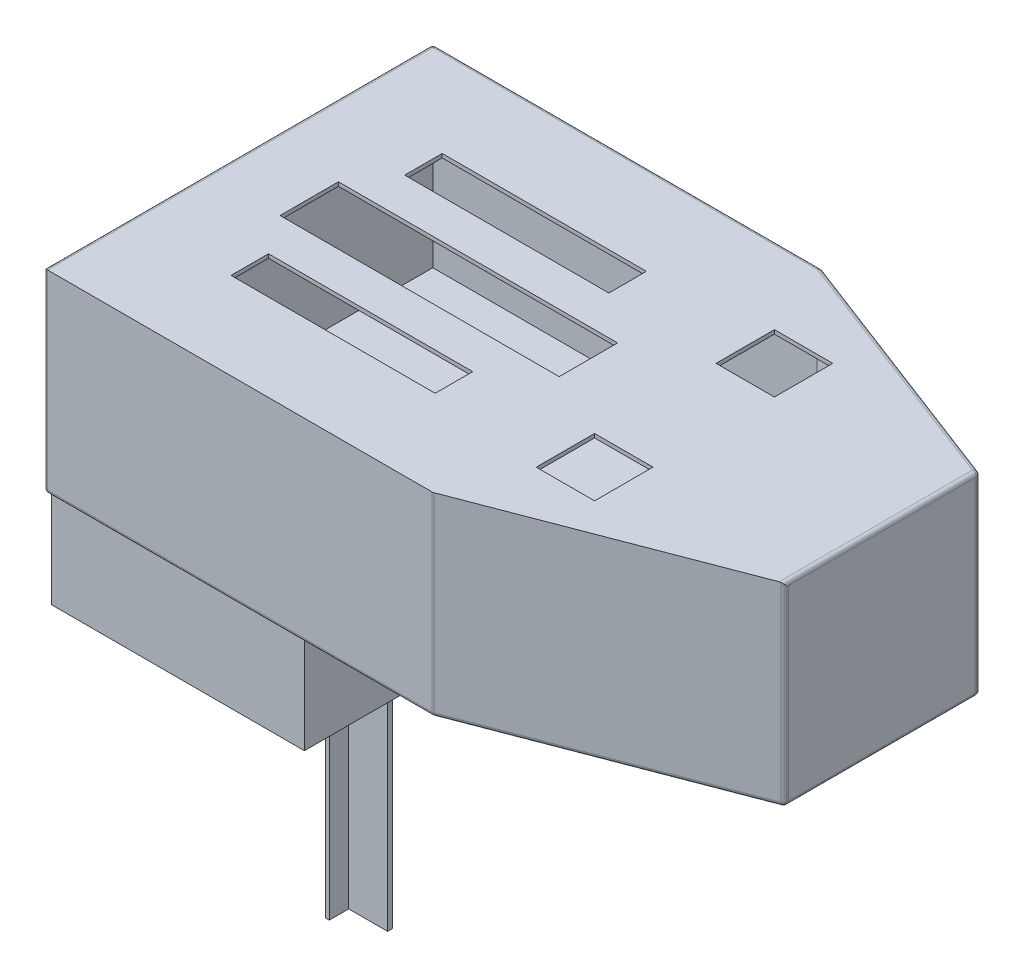
SolidWorks part; units mm, degrees
material "Polyurethane Foam Rigid"
ref_plane "Front Plane" through (0, 0, 0) normal (0, 0, 1) x (1, 0, 0)
ref_plane "Top Plane" through (0, 0, 0) normal (0, 1, 0) x (1, 0, 0)
ref_plane "Right Plane" through (0, 0, 0) normal (1, 0, 0) x (0, 0, -1)
sketch "Sketch1" plane through (0, 0, 0) normal (0, 1, 0) x (1, 0, 0)
  line L0 (74.2268, 57.732) -> (139.6103, 32.732)
  line L1 (-25.7732, 57.732) -> (74.2268, 57.732)
  line L2 (-25.7732, 57.732) -> (-25.7732, -42.268)
  line L3 (-25.7732, -42.268) -> (74.2268, -42.268)
  line L5 (139.6103, 32.732) -> (139.6103, -17.268)
  line L6 (139.6103, -17.268) -> (74.2268, -42.268)
  dimension "D1" = 100
  dimension "D2" = 100
  dimension "D3" = 50
  dimension "D4" = 25
  dimension "D5" = 70
extrude "Boss-Extrude1" add sketch "Sketch1" along normal mid plane 50
shell "Shell1" thickness 1 removed face at (139.6103, 0, -7.732) removed face at (-25.7732, 0, -7.732)
sketch "Sketch2" plane through (0, 0, 0) normal (1, 0, 0) x (0, 0, -1)
  line L0 (-16.1974, -24) -> (31.6614, -24) construction
  line L1 (-16.1974, 24) -> (31.6614, 24)
  line L2 (-16.1974, 24) -> (-16.1974, -24)
  line L3 (-16.1974, -24) -> (31.6614, -24)
  line L4 (31.6614, 24) -> (31.6614, -24)
  line L5 (31.6614, 24) -> (31.6614, -24) construction
extrude "Boss-Extrude5" add sketch "Sketch2" against normal blind 1 from surface separate body starting at face at (139.6103, 0, -7.732)
sketch "Sketch3" plane through (0, 0, 0) normal (1, 0, 0) x (0, 0, -1)
  line L1 (56.732, 24) -> (-41.268, 24)
  line L2 (56.732, 24) -> (56.732, -24)
  line L3 (56.732, -24) -> (-41.268, -24)
  line L4 (-41.268, 24) -> (-41.268, -24)
extrude "Boss-Extrude6" add sketch "Sketch3" along normal blind 1 from surface starting at face at (-25.7732, 0, -7.732)
fillet "Fillet1" radius 1 19 edges at (139.6103, 0, 17.268) (139.6103, 25, -7.732) (139.6103, 0, -32.732) (139.6103, -25, -7.732) (74.2268, 0, -57.732) (74.0421, 0, -56.732) (106.9185, -25, 29.768) (74.2268, 0, 42.268) (106.8262, 24, 28.7327) (24.2268, -25, 42.268) (24.6345, 24, 41.268) (106.9185, -25, -45.232) (106.9185, 25, -45.232) (24.2268, 25, -57.732) (24.2268, -25, -57.732) (-25.7732, 0, 42.268) (-25.7732, 25, -7.732) (-25.7732, -25, -7.732) (-25.7732, 0, -57.732)
sketch "Sketch4" plane through (0, 0, 0) normal (0, 1, 0) x (1, 0, 0)
  line L1 (-7.03, 14.732) -> (64.7036, 14.732)
  line L2 (-7.03, 14.732) -> (-7.03, -0.268)
  line L3 (-7.03, -0.268) -> (64.7036, -0.268)
  line L4 (64.7036, 14.732) -> (64.7036, -0.268)
  dimension "D1" = 15
extrude "Cut-Extrude1" cut sketch "Sketch4" against normal blind 1 from surface starting at face at (64.3087, 25, -0.1575)
sketch "Sketch5" plane through (0, 0, 0) normal (0, 1, 0) x (1, 0, 0)
  line L9 (81.8965, 37.843) -> (96.8965, 37.843)
  line L11 (81.8965, 37.843) -> (81.8965, 22.843)
  line L12 (81.8965, 22.843) -> (96.8965, 22.843)
  line L14 (96.8965, 37.843) -> (96.8965, 22.843)
  line L17 (81.8965, -8.3631) -> (96.8965, -8.3631)
  line L18 (81.8965, -8.3631) -> (81.8965, -23.3631)
  line L19 (81.8965, -23.3631) -> (96.8965, -23.3631)
  line L20 (96.8965, -8.3631) -> (96.8965, -23.3631)
  point P8 (-105.2687, 71.4523)
  dimension "D1" = 15
  dimension "D2" = 15
  dimension "D3" = 15
extrude "Cut-Extrude3" cut sketch "Sketch5" against normal blind 1 from surface starting at face at (64.3087, 25, -0.1575)
sketch "Sketch6" plane through (0, -25, 0) normal (0, -1, 0) x (1, 0, 0)
  line L1 (5.1304, 0.7852) -> (6.1304, 0.7852)
  line L2 (5.1304, 0.7852) -> (5.1304, -9.2148)
  line L3 (5.1304, -9.2148) -> (6.1304, -9.2148)
  line L4 (6.1304, 0.7852) -> (6.1304, -9.2148)
  dimension "D1" = 10
  dimension "D2" = 1
sketch "Sketch7" plane through (0, -25, 0) normal (0, -1, 0) x (1, 0, 0)
  line L6 (-24.7732, 41.268) -> (-24.7732, -56.732)
  line L7 (-24.7732, -56.732) -> (40.2268, -56.732)
  line L8 (-24.7732, -56.732) -> (74.0421, -56.732) construction
  line L9 (40.2268, -56.732) -> (40.2268, 41.268)
  line L10 (74.0421, 41.268) -> (-24.7732, 41.268) construction
  line L11 (40.2268, 41.268) -> (-24.7732, 41.268)
  dimension "D1" = 65
extrude "Boss-Extrude8" add sketch "Sketch7" along normal blind 25
sketch "Sketch8" plane through (0, -50, 0) normal (0, -1, 0) x (1, 0, 0)
  line L1 (6.1304, -5.5077) -> (16.1304, -5.5077)
  line L2 (6.1304, -5.5077) -> (6.1304, -4.2148)
  line L3 (6.1304, -4.2148) -> (16.1304, -4.2148)
  line L4 (16.1304, -5.5077) -> (16.1304, -4.2148)
  dimension "D1" = 10
extrude "Boss-Extrude10" add sketch "Sketch6" along normal blind 75 from surface contours L4 L3 L2 L1 starting at face at (7.7268, -50, -7.732)
extrude "Boss-Extrude11" add sketch "Sketch8" along normal blind 75
sketch "Sketch9" plane through (0, 25, 0) normal (0, 1, 0) x (1, 0, 0)
  line L1 (0, 34.3706) -> (52.47, 34.3706)
  line L2 (0, 34.3706) -> (0, 24.732)
  line L3 (0, 24.732) -> (52.47, 24.732)
  line L4 (52.47, 34.3706) -> (52.47, 24.732)
  line L5 (0, -10.268) -> (52.47, -10.268)
  line L6 (0, -10.268) -> (0, -19.9067)
  line L7 (0, -19.9067) -> (52.47, -19.9067)
  line L8 (52.47, -10.268) -> (52.47, -19.9067)
extrude "Cut-Extrude4" cut sketch "Sketch9" against normal blind 1
